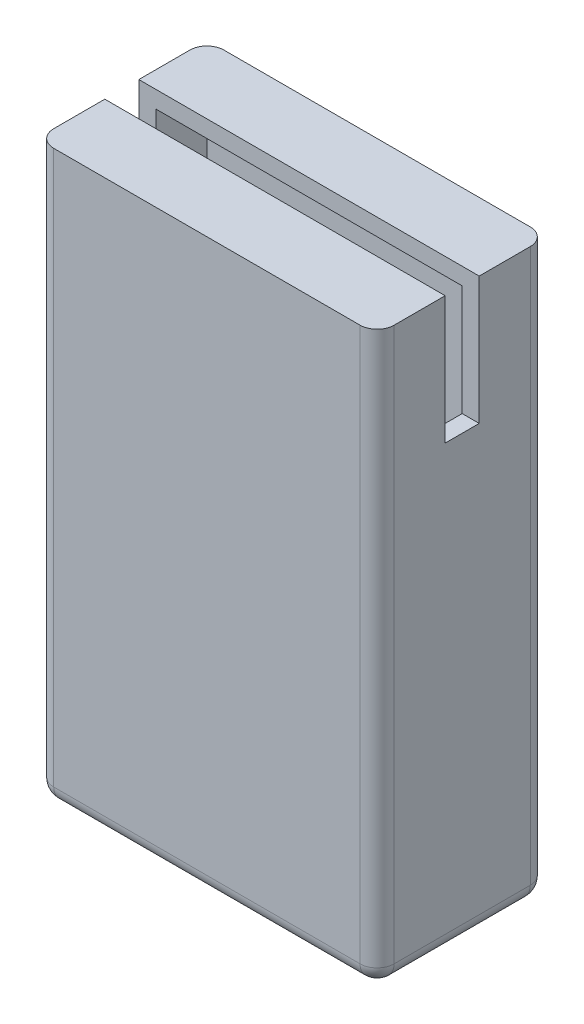
SolidWorks part; units mm, degrees
ref_plane "Alzado" through (0, 0, 0) normal (0, 0, 1) x (1, 0, 0)
ref_plane "Planta" through (0, 0, 0) normal (0, 1, 0) x (1, 0, 0)
ref_plane "Vista lateral" through (0, 0, 0) normal (1, 0, 0) x (0, 0, -1)
sketch "Croquis1" plane through (0, 0, 0) normal (0, 0, 1) x (1, 0, 0)
  line L1 (-20, -33.5) -> (20, -33.5)
  line L2 (-20, -33.5) -> (-20, 33.5)
  line L3 (-20, 33.5) -> (20, 33.5)
  line L4 (20, -33.5) -> (20, 33.5)
  line L5 (-20, -33.5) -> (20, 33.5) construction
  line L6 (-20, 33.5) -> (20, -33.5) construction
  point P0 (0, 0)
  dimension "D1" = 40
  dimension "D2" = 67
extrude "Saliente-Extruir1" add sketch "Croquis1" along normal blind 20
fillet "Redondeo1" radius 2 8 edges at (0, -33.5, 20) (-20, 0, 20) (0, -33.5, 0) (-20, 0, 0) (20, 0, 0) (20, 0, 20) (-20, -33.5, 10) (20, -33.5, 10)
shell "Vaciado1" thickness 2 removed face at (0, -33.5, 10)
sketch "Croquis2" plane through (0, 33.5, 0) normal (0, 1, 0) x (1, 0, 0)
  line L0 (-20, -12) -> (20, -12)
  line L1 (-20, -12) -> (-20, -8)
  line L2 (20, -12) -> (20, -8)
  line L3 (-20, -8) -> (20, -8)
  line L4 (-20, -12) -> (20, -8) construction
  line L5 (20, -12) -> (-20, -8) construction
  line L6 (-19.4142, -0.5858) -> (19.4142, -19.4142) construction
  line L7 (19.4142, -0.5858) -> (-19.4142, -19.4142) construction
  arc A0 (-18, 0) -> (-20, -2) centre (-18, -2) ccw construction
  arc A1 (18, -20) -> (20, -18) centre (18, -18) ccw construction
  arc A2 (20, -2) -> (18, 0) centre (18, -2) ccw construction
  arc A3 (-20, -18) -> (-18, -20) centre (-18, -18) ccw construction
  point P1 (0, -10)
  point P26 (0, -10)
  dimension "D1" = 4
  dimension "D2" = 40
extrude "Cortar-Extruir1" cut sketch "Croquis2" against normal blind 15
